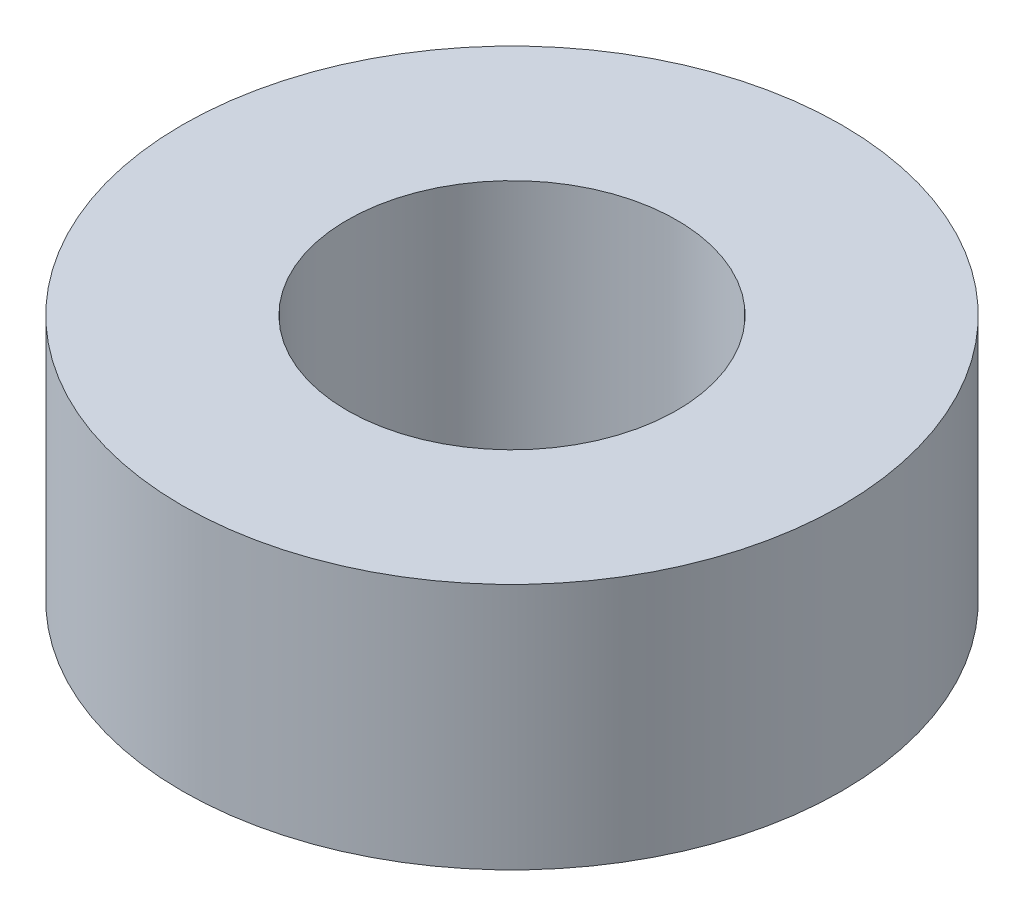
SolidWorks part; units mm, degrees
ref_plane "Front Plane" through (0, 0, 0) normal (0, 0, 1) x (1, 0, 0)
ref_plane "Top Plane" through (0, 0, 0) normal (0, 1, 0) x (1, 0, 0)
ref_plane "Right Plane" through (0, 0, 0) normal (1, 0, 0) x (0, 0, -1)
sketch "Sketch1" plane through (0, 0, 0) normal (0, 1, 0) x (1, 0, 0)
  circle A0 centre (0, 0) radius 2
  circle A1 centre (0, 0) radius 4
  dimension "D1" = 4
  dimension "D2" = 8
extrude "Boss-Extrude1" add sketch "Sketch1" along normal blind 1.5 and the other way blind 1.5
